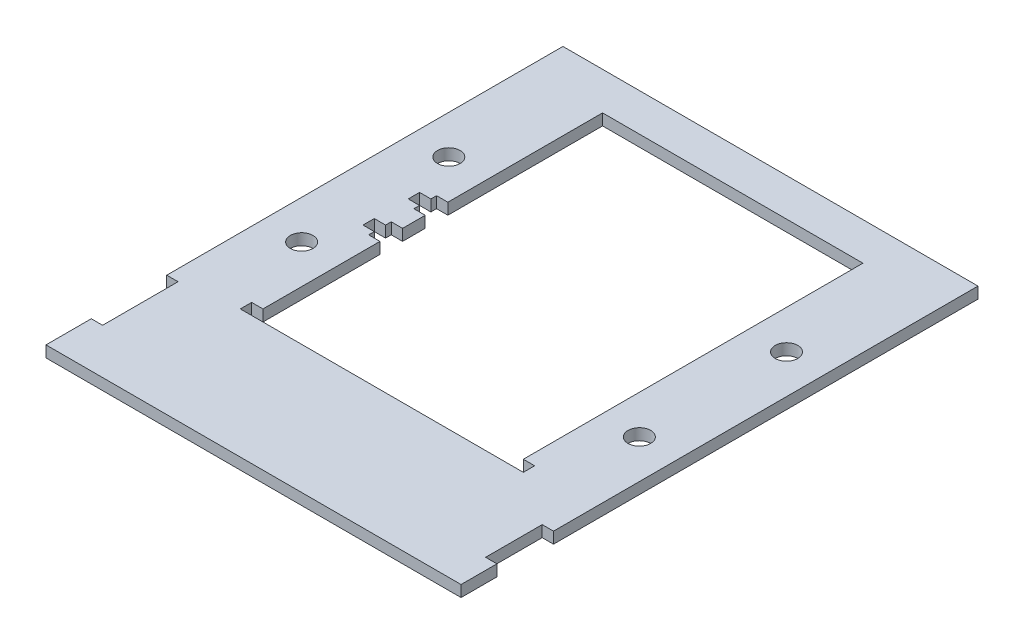
SolidWorks part; units mm, degrees
ref_plane "Alzado" through (0, 0, 0) normal (0, 0, 1) x (1, 0, 0)
ref_plane "Planta" through (0, 0, 0) normal (0, 1, 0) x (1, 0, 0)
ref_plane "Vista lateral" through (0, 0, 0) normal (1, 0, 0) x (0, 0, -1)
sketch "Croquis1" plane through (0, 0, 0) normal (0, 1, 0) x (1, 0, 0)
  line L0 (99.75, 99.5) -> (99.75, 60.5) construction
  line L1 (110, 3) -> (110, 12.5)
  line L2 (89.5, 37) -> (20.5, 37)
  line L3 (3, 20) -> (3, 15)
  line L4 (110, 27.5) -> (110, 37)
  line L5 (89.5, 71) -> (89.5, 89)
  line L6 (110, 3) -> (110, 12.5)
  line L7 (110, 140) -> (89.5, 140)
  line L8 (14.5, 86) -> (10.25, 86) construction
  line L9 (107, 12.5) -> (110, 12.5)
  line L10 (107, 27.5) -> (110, 27.5)
  line L11 (107, 20) -> (107, 12.5)
  line L12 (20.5, 140) -> (89.5, 140)
  line L13 (89.5, 130) -> (20.5, 130)
  line L14 (110, 27.5) -> (110, 140)
  line L15 (0, 50) -> (0, 35)
  line L16 (17.5, 87.5) -> (14.5, 87.5)
  line L17 (0, 15) -> (0, 3)
  line L18 (3, 35) -> (0, 35)
  line L19 (3, 15) -> (0, 15)
  line L20 (20.5, 37) -> (17.5, 37)
  line L21 (17.5, 37) -> (17.5, 40)
  line L22 (107, 20) -> (107, 27.5)
  line L23 (0, 140) -> (20.5, 140)
  line L24 (3, 20) -> (3, 35)
  line L25 (55, 130) -> (55, 37) construction
  line L26 (17.5, 40) -> (20.5, 40)
  line L27 (14.5, 87.5) -> (14.5, 84.5)
  line L28 (92.5, 40) -> (89.5, 40)
  line L29 (92.5, 37) -> (92.5, 40)
  line L30 (0, 50) -> (0, 140)
  line L31 (89.5, 37) -> (92.5, 37)
  line L32 (110, 3) -> (0, 3)
  line L33 (17.5, 84.5) -> (14.5, 84.5)
  line L34 (89.5, 89) -> (89.5, 130)
  line L35 (89.5, 71) -> (89.5, 40)
  line L36 (17.5, 87.5) -> (17.5, 89)
  line L37 (17.5, 72.5) -> (14.5, 72.5)
  line L38 (14.5, 72.5) -> (14.5, 75.5)
  line L39 (10.25, 80) -> (20.5, 80) construction
  line L40 (10.25, 99.5) -> (10.25, 60.5) construction
  line L41 (20.5, 77) -> (17.5, 77)
  line L42 (17.5, 71) -> (20.5, 71)
  line L43 (20.5, 71) -> (20.5, 40)
  line L44 (20.5, 89) -> (20.5, 130)
  line L45 (17.5, 89) -> (20.5, 89)
  line L46 (17.5, 40) -> (20.5, 40)
  line L47 (20.5, 83) -> (17.5, 83)
  line L48 (20.5, 77) -> (20.5, 83)
  line L49 (17.5, 77) -> (17.5, 75.5)
  line L50 (17.5, 83) -> (17.5, 84.5)
  line L51 (17.5, 75.5) -> (14.5, 75.5)
  line L52 (17.5, 72.5) -> (17.5, 71)
  circle A0 centre (99.75, 60.5) radius 3
  circle A1 centre (99.75, 99.5) radius 3
  circle A2 centre (10.25, 99.5) radius 3
  circle A3 centre (10.25, 60.5) radius 3
  point P33 (55, 130)
  point P34 (55, 140)
  point P48 (14.5, 86)
  dimension "D7" = 6
  dimension "D9" = 6
  dimension "D36" = 6
  dimension "D37" = 6
  dimension "D38" = 10.25
  dimension "D1" = 15
  dimension "D2" = 3
  dimension "D3" = 20.5
  dimension "D4" = 57.5
  dimension "D5" = 39
  dimension "D6" = 5
  dimension "D8" = 3
  dimension "D10" = 3
  dimension "D11" = 6
  dimension "D12" = 3
  dimension "D13" = 3
  dimension "D14" = 1.5
  dimension "D15" = 3
  dimension "D16" = 1.5
  dimension "D17" = 6
  dimension "D18" = 3
  dimension "D19" = 6
  dimension "D20" = 3
  dimension "D21" = 31
  dimension "D22" = 3
  dimension "D23" = 34
  dimension "D24" = 12
  dimension "D25" = 3
  dimension "D26" = 110
  dimension "D27" = 15
  dimension "D28" = 90
  dimension "D29" = 69
  dimension "D30" = 18
  dimension "D31" = 41
  dimension "D32" = 69
  dimension "D33" = 69
  dimension "D34" = 20.5
  dimension "D35" = 20.5
  dimension "D39" = 9.5
  dimension "D40" = 7.5
  dimension "D41" = 7.5
  dimension "D42" = 9.5
  dimension "D43" = 1.5
extrude "Saliente-Extruir1" add sketch "Croquis1" along normal blind 3 contours L18 L1 L9 L11 L22 L10 L4 L14 L7 L12 L23 A2 A1 A0 L2 L13 A3 region at (55, 0, -4.757)
